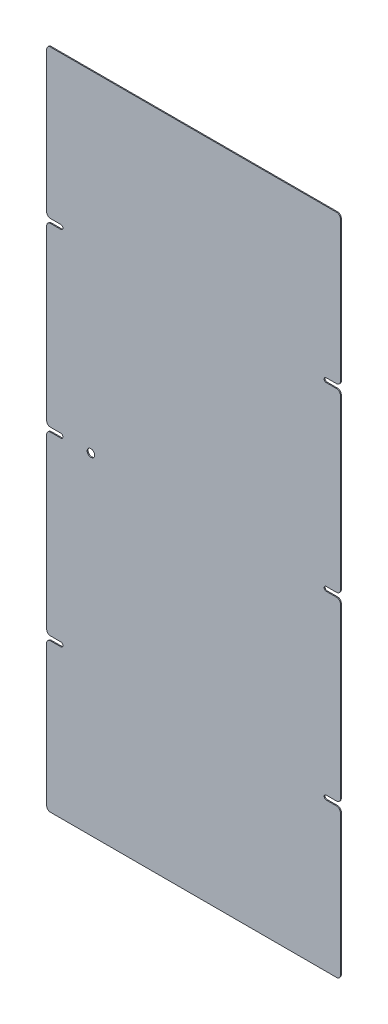
SolidWorks part; units mm, degrees
material "6061-T6 (SS)"
ref_plane "Plane1" through (0, 0, 0) normal (0, 0, 1) x (1, 0, 0)
ref_plane "Plane2" through (0, 0, 0) normal (0, 1, 0) x (1, 0, 0)
ref_plane "Plane3" through (0, 0, 0) normal (1, 0, 0) x (0, 0, -1)
ref_axis "Axis1" through (-83.9706, 0, 0) along (1, 0, 0)
ref_axis "Axis2" through (0, 0, -0.0794) along (0, 0, 1)
ref_axis "Axis3" through (0, 614.68, 0) along (0, -1, 0)
sketch "Sketch1" plane through (0, 0, 0) normal (0, 0, 1) x (1, 0, 0)
  line L0 (0, 0) -> (223.8375, 0) construction
  line L1 (-247.65, -558.8) -> (247.65, -558.8)
  line L2 (-247.65, -558.8) -> (-247.65, 558.8)
  line L3 (-247.65, 558.8) -> (247.65, 558.8)
  line L4 (247.65, -558.8) -> (247.65, 558.8)
  line L5 (-247.65, -558.8) -> (247.65, 558.8) construction
  line L6 (-247.65, 558.8) -> (247.65, -558.8) construction
  line L7 (50, 0) -> (-50, 0) construction
  line L8 (223.8375, 0) -> (223.8375, 558.8) construction
  line L9 (0, 0) -> (0, 126.2517) construction
  circle A0 centre (223.8375, 304.8) radius 3.5687
  circle A1 centre (223.8375, -304.8) radius 3.5687
  circle A2 centre (223.8375, 0) radius 3.5687
  circle A3 centre (-223.8375, -304.8) radius 3.5687
  circle A4 centre (-223.8375, 0) radius 3.5687
  circle A5 centre (-223.8375, 304.8) radius 3.5687
  point P0 (0, 0)
  dimension "D4" = 7.1374
  dimension "D1" = 495.3
  dimension "D2" = 1117.6
  dimension "D3" = 447.675
  dimension "D5" = 609.6
extrude "Boss-Extrude1" add sketch "Sketch1" along normal blind 1.5875
sketch "Sketch2" plane through (0, 0, 1.5875) normal (0, 0, 1) x (1, 0, 0)
  line L0 (-223.8375, 304.8) -> (-276.9155, 304.8) construction
  line L1 (-223.8375, 301.2313) -> (-276.9155, 301.2313)
  line L2 (-223.8375, 308.3687) -> (-276.9155, 308.3687)
  line L3 (-223.8375, 0) -> (-306.2761, 0) construction
  line L4 (-223.8375, -3.5687) -> (-306.2761, -3.5687)
  line L5 (-223.8375, 3.5687) -> (-306.2761, 3.5687)
  line L6 (304.875, 304.8) -> (223.8375, 304.8) construction
  line L7 (304.875, 301.2313) -> (223.8375, 301.2313)
  line L8 (304.875, 308.3687) -> (223.8375, 308.3687)
  line L9 (299.8583, 0) -> (223.8375, 0) construction
  line L10 (299.8583, -3.5687) -> (223.8375, -3.5687)
  line L11 (299.8583, 3.5687) -> (223.8375, 3.5687)
  line L12 (308.3599, -304.8) -> (223.8375, -304.8) construction
  line L13 (308.3599, -308.3687) -> (223.8375, -308.3687)
  line L14 (308.3599, -301.2313) -> (223.8375, -301.2313)
  line L15 (-223.8375, -304.8) -> (-314.956, -304.8) construction
  line L16 (-223.8375, -308.3687) -> (-314.956, -308.3687)
  line L17 (-223.8375, -301.2313) -> (-314.956, -301.2313)
  arc A0 (-223.8375, 301.2313) -> (-223.8375, 308.3687) centre (-223.8375, 304.8) ccw
  arc A1 (-276.9155, 308.3687) -> (-276.9155, 301.2313) centre (-276.9155, 304.8) ccw
  arc A5 (-223.8375, -3.5687) -> (-223.8375, 3.5687) centre (-223.8375, 0) ccw
  arc A6 (-306.2761, 3.5687) -> (-306.2761, -3.5687) centre (-306.2761, 0) ccw
  arc A7 (304.875, 301.2313) -> (304.875, 308.3687) centre (304.875, 304.8) ccw
  arc A8 (223.8375, 308.3687) -> (223.8375, 301.2313) centre (223.8375, 304.8) ccw
  arc A9 (299.8583, -3.5687) -> (299.8583, 3.5687) centre (299.8583, 0) ccw
  arc A10 (223.8375, 3.5687) -> (223.8375, -3.5687) centre (223.8375, 0) ccw
  arc A11 (308.3599, -308.3687) -> (308.3599, -301.2313) centre (308.3599, -304.8) ccw
  arc A12 (223.8375, -301.2313) -> (223.8375, -308.3687) centre (223.8375, -304.8) ccw
  arc A13 (-223.8375, -308.3687) -> (-223.8375, -301.2313) centre (-223.8375, -304.8) ccw
  arc A14 (-314.956, -301.2313) -> (-314.956, -308.3687) centre (-314.956, -304.8) ccw
  point P3 (-250.3765, 304.8)
  point P10 (-265.0568, 0)
  point P17 (264.3563, 304.8)
  point P24 (261.8479, 0)
  point P31 (266.0987, -304.8)
  point P38 (-269.3967, -304.8)
  dimension "D1" = 3.5687
  dimension "D2" = 3.5687
  dimension "D3" = 3.5687
  dimension "D4" = 3.5687
  dimension "D5" = 3.5687
  dimension "D6" = 3.5687
extrude "Cut-Extrude1" cut sketch "Sketch2" against normal through all
fillet "Fillet1" radius 6.35 16 edges at (247.65, -558.8, 0.7937) (-247.65, 558.8, 0.7937) (247.65, 558.8, 0.7937) (-247.65, -558.8, 0.7937) (-247.65, -301.2313, 0.7937) (-247.65, -3.5687, 0.7937) (-247.65, 3.5687, 0.7937) (-247.65, 301.2313, 0.7937) (-247.65, 308.3687, 0.7937) (247.65, 308.3687, 0.7937) (247.65, 301.2313, 0.7937) (247.65, 3.5687, 0.7937) (247.65, -3.5687, 0.7937) (247.65, -301.2313, 0.7937) (247.65, -308.3687, 0.7937) (-247.65, -308.3687, 0.7937)
sketch "Sketch3" plane through (0, 0, 0) normal (0, 0, -1) x (-1, 0, 0)
  line L0 (0, 0) -> (173.0375, 0) construction
  circle A3 centre (173.0375, 0) radius 6.35
  dimension "D1" = 12.7
  dimension "D2" = 173.0375
extrude "Cut-Extrude2" cut sketch "Sketch3" against normal through all
